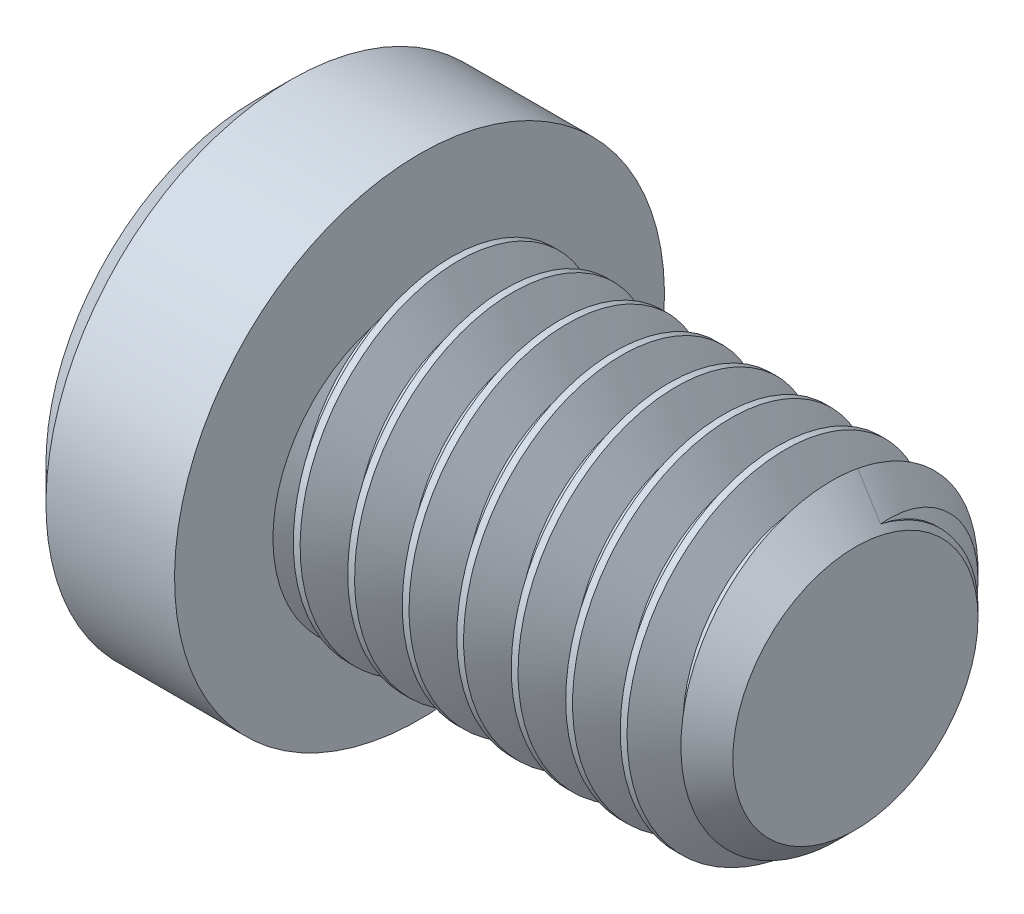
SolidWorks part; units mm, degrees
material "Alloy Steel"
ref_plane "Front Plane" through (0, 0, 0) normal (0, 0, 1) x (1, 0, 0)
ref_plane "Top Plane" through (0, 0, 0) normal (0, 1, 0) x (1, 0, 0)
ref_plane "Right Plane" through (0, 0, 0) normal (1, 0, 0) x (0, 0, -1)
sketch "Sketch1" plane through (0, 0, 0) normal (0, 0, 1) x (1, 0, 0)
  line L0 (6.35, 0) -> (-6.35, 0) construction
  line L1 (6.35, 4.7625) -> (6.35, -4.7625) construction
  line L2 (-6.35, 7.1374) -> (-6.35, -7.1374) construction
  line L3 (-6.35, 7.1374) -> (-10.0965, 7.1374) construction
  line L4 (-10.0965, 7.1374) -> (-11.1125, 6.1214) construction
  line L5 (-11.1125, 6.1214) -> (-11.1125, -6.1214) construction
  line L6 (-11.1125, -6.1214) -> (-10.0965, -7.1374) construction
  line L7 (-10.0965, -7.1374) -> (-6.35, -7.1374) construction
  point P7 (-8.1915, 0)
  point P12 (0, -4.7625)
  dimension "D1" = 45
  dimension "Dec." = 9.525
  dimension "Length" = 12.7
  dimension "Head Dia" = 14.2748
  dimension "Head Height" = 4.7625
  dimension "Hex Depth" = 2.921
  dimension "Chamfer" = 1.016
  dimension "D2" = 6.35
ref_plane "Plane1" through (6.35, 0, 0) normal (1, 0, 0) x (0, 0, -1)
ref_plane "Plane2" through (-11.1125, 0, 0) normal (1, 0, 0) x (0, 0, -1)
sketch "Sketch2" plane through (6.35, 0, 0) normal (1, 0, 0) x (0, 0, -1)
  circle A0 centre (0, 0) radius 4.7625
extrude "Boss-Extrude1" add sketch "Sketch2" against normal up to vertex (12.7 mm away) up to point (-6.35, 0, 0)
sketch "Sketch3" plane through (6.35, 0, 0) normal (1, 0, 0) x (0, 0, -1)
  circle A0 centre (0, 0) radius 4.7625 construction
  circle A1 centre (0, 0) radius 4.7625
curve "Helix/Spiral1" pitch 1.5875 height 14.2875 radius 4.7625 centre (6.35, 0, 0) axis (-1, 0, 0) start towards (0, 1, 0) parameters "Pitch"=1.5875
chamfer "Chamfer1" distance 1.1906 angle 45 1 edges at (6.35, 0, -4.7625)
sketch "Sketch5" plane through (0, 0, 0) normal (0, 0, 1) x (1, 0, 0)
  line L0 (5.6555, 4.7625) -> (7.0445, 4.7625)
  line L1 (7.0445, 4.7625) -> (6.4492, 3.7314)
  line L2 (6.4492, 3.7314) -> (6.2508, 3.7314)
  line L3 (6.2508, 3.7314) -> (5.6555, 4.7625)
  line L4 (6.35, 3.7314) -> (6.35, 4.7625) construction
  line L5 (5.9531, 4.2469) -> (6.7469, 4.2469) construction
  dimension "D1" = 60
  dimension "D2" = 0.7937
  dimension "D3" = 0.1984
sweep "Cut-Sweep1" cut profiles "Sketch5" path "Helix/Spiral1" align with end faces yes
sketch "Sketch4" plane through (-11.1125, 0, 0) normal (1, 0, 0) x (0, 0, -1)
  line L0 (-7.1374, 0.7937) -> (7.1374, 0.7937) construction
  line L1 (0, 2.7496) -> (-2.3813, 1.3748)
  line L2 (-2.3813, 1.3748) -> (-2.3812, -1.3748)
  line L3 (-2.3812, -1.3748) -> (0, -2.7496)
  line L4 (0, -2.7496) -> (2.3813, -1.3748)
  line L5 (2.3813, -1.3748) -> (2.3812, 1.3748)
  line L6 (2.3812, 1.3748) -> (0, 2.7496)
  line L7 (0, 0) -> (0, 0.7937) construction
  circle A0 centre (0, 0) radius 2.3813 construction
  dimension "D2" = 0.7937
  dimension "Hex Size" = 4.7625
  dimension "D1" = 14.2748
sketch "Sketch6" plane through (0, 0, 0) normal (0, 0, 1) x (1, 0, 0)
  line L0 (-10.0965, 7.1374) -> (-11.1125, 6.1214) construction
  line L1 (-6.35, 7.1374) -> (-10.0965, 7.1374) construction
  line L2 (-6.35, 7.1374) -> (-6.35, -7.1374) construction
  line L3 (-11.1125, 6.1214) -> (-11.1125, -6.1214) construction
  line L4 (-10.0965, 7.1374) -> (-11.1125, 6.1214)
  line L5 (-6.35, 7.1374) -> (-10.0965, 7.1374)
  line L6 (-6.35, 7.1374) -> (-6.35, 0)
  line L7 (-11.1125, 6.1214) -> (-11.1125, 0)
  line L8 (-6.35, 0) -> (-11.1125, 0) construction
  line L9 (-6.35, 0) -> (-11.1125, 0)
revolve "Revolve1" add sketch "Sketch6" angle 360 about L8
extrude "Cut-Extrude1" cut sketch "Sketch4" along normal up to vertex (2.921 mm away) up to point (-8.1915, 0, 0)
sketch "Sketch8" plane through (-11.1125, 0, 0) normal (-1, 0, 0) x (0, 0, 1)
  circle A1 centre (0, 0) radius 2.7496
extrude "Cut-Extrude2" cut sketch "Sketch8" against normal through all draft 45
equation "\"D3@Helix/Spiral1\" = \"Length@Sketch1\"+\"Pitch@Helix/Spiral1\""
equation "\"D3@Sketch5\" = \"Pitch@Helix/Spiral1\"*.125"
equation "\"D2@Sketch5\" = \"Pitch@Helix/Spiral1\"*.50"
equation "\"D1@Chamfer1\" = \"Pitch@Helix/Spiral1\"*.75"
equation "\"D2@Sketch1\" = \"Pitch@Helix/Spiral1\"*4"
equation "\"D1@Sketch4\" = \"Head Dia@Sketch1\""
